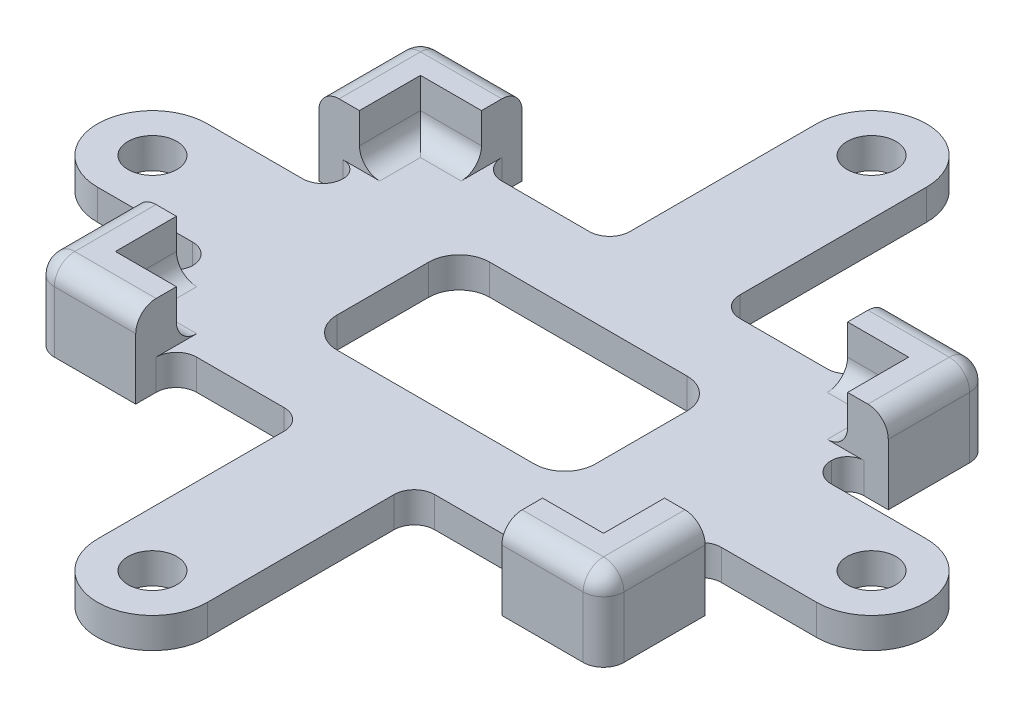
SolidWorks part; units mm, degrees
ref_plane "Front Plane" through (0, 0, 0) normal (0, 0, 1) x (1, 0, 0)
ref_plane "Top Plane" through (0, 0, 0) normal (0, 1, 0) x (1, 0, 0)
ref_plane "Right Plane" through (0, 0, 0) normal (1, 0, 0) x (0, 0, -1)
sketch "Sketch1" plane through (0, 0, 0) normal (0, 1, 0) x (1, 0, 0)
  line L0 (-12, 7.5) -> (12, 7.5)
  line L1 (-11, -6.5) -> (11, -6.5) construction
  line L2 (-11, -6.5) -> (-11, 6.5) construction
  line L3 (-11, 6.5) -> (11, 6.5) construction
  line L4 (11, -6.5) -> (11, 6.5) construction
  line L5 (-11, -6.5) -> (11, 6.5) construction
  line L6 (-11, 6.5) -> (11, -6.5) construction
  line L7 (12, -7.5) -> (12, 7.5)
  line L8 (-12, -7.5) -> (12, -7.5)
  line L9 (-12, -7.5) -> (-12, 7.5)
  point P0 (0, 0)
  point P10 (0, 0)
  point P16 (0, 0)
  dimension "D1" = 13
  dimension "D2" = 22
  dimension "D3" = 1
extrude "Boss-Extrude1" add sketch "Sketch1" along normal mid plane 1.5
sketch "Sketch2" plane through (0, 0.75, 0) normal (0, 1, 0) x (1, 0, 0)
  line L0 (-12, 4.5) -> (-14, 4.5)
  line L1 (-12, 7.5) -> (-12, -7.5) construction
  line L2 (-14, 4.5) -> (-14, 9.5)
  line L3 (-14, 9.5) -> (-9, 9.5)
  line L4 (-9, 9.5) -> (-9, 7.5)
  line L5 (12, 7.5) -> (-12, 7.5) construction
  line L6 (-9, 7.5) -> (-12, 7.5)
  line L7 (-12, 7.5) -> (-12, 4.5)
  dimension "D1" = 3
  dimension "D2" = 2
extrude "Boss-Extrude2" add sketch "Sketch2" along normal blind 2.5 and the other way blind 1.5
mirror "Mirror1" about plane through (0, 0, 0) normal (1, 0, 0) of "Boss-Extrude2"
mirror "Mirror2" about plane through (0, 0, 0) normal (0, 0, 1) of "Mirror1", "Boss-Extrude2"
sketch "Sketch3" plane through (0, 0.75, 0) normal (0, 1, 0) x (1, 0, 0)
  line L0 (0, -17.6777) -> (-17.6777, 0) construction
  line L1 (0, -17.6777) -> (17.6777, 0) construction
  line L2 (-17.6777, 0) -> (0, 17.6777) construction
  line L3 (17.6777, 0) -> (0, 17.6777) construction
  line L4 (0, -17.6777) -> (0, 17.6777) construction
  line L5 (-17.6777, 0) -> (17.6777, 0) construction
  line L6 (-17.6777, 2.7) -> (-12, 2.7)
  line L7 (-12, 4.5) -> (-12, -4.5) construction
  line L8 (-12, 2.7) -> (-12, -2.7)
  line L9 (-12, -2.7) -> (-17.6777, -2.7)
  line L10 (-2.7, 17.6777) -> (-2.7, 7.5)
  line L11 (9, 7.5) -> (-9, 7.5) construction
  line L12 (-2.7, 7.5) -> (2.7, 7.5)
  line L13 (2.7, 7.5) -> (2.7, 17.6777)
  line L14 (12, -2.7) -> (17.6777, -2.7)
  line L15 (12, 2.7) -> (12, -2.7)
  line L16 (17.6777, 2.7) -> (12, 2.7)
  line L17 (-2.7, -7.5) -> (2.7, -7.5)
  line L18 (-2.7, -17.6777) -> (-2.7, -7.5)
  line L19 (2.7, -7.5) -> (2.7, -17.6777)
  circle A0 centre (-17.6777, 0) radius 1.2
  arc A1 (-17.6777, 2.7) -> (-17.6777, -2.7) centre (-17.6777, 0) ccw
  circle A2 centre (-17.6777, 0) radius 2.7 construction
  circle A3 centre (0, 17.6777) radius 1.2
  arc A4 (-2.7, 17.6777) -> (2.7, 17.6777) centre (0, 17.6777) cw
  circle A5 centre (17.6777, 0) radius 1.2
  arc A6 (17.6777, 2.7) -> (17.6777, -2.7) centre (17.6777, 0) cw
  circle A7 centre (0, -17.6777) radius 1.2
  arc A8 (-2.7, -17.6777) -> (2.7, -17.6777) centre (0, -17.6777) ccw
  point P1 (0, 0)
  point P17 (-7.2196, 17.6777)
  dimension "D2" = 2.4
  dimension "D1" = 25
  dimension "D3" = 1.5
extrude "Boss-Extrude3" add sketch "Sketch3" against normal up to surface (1.5 mm away) up to face at (0, -0.75, 0)
fillet "Fillet1" radius 1 28 edges at (-14, 1.25, 9.5) (-14, 3.25, 7) (-11.5, 3.25, 9.5) (14, 1.25, 9.5) (11.5, 3.25, 9.5) (14, 3.25, 7) (14, 1.25, -9.5) (14, 3.25, -7) (11.5, 3.25, -9.5) (-11.5, 3.25, -9.5) (-14, 3.25, -7) (-14, 1.25, -9.5) (-10.5, 0.75, -7.5) (-12, 0.75, -6) (10.5, 0.75, -7.5) (12, 0.75, -6) (12, 0.75, 6) (10.5, 0.75, 7.5) (-10.5, 0.75, 7.5) (-12, 0.75, 6) (2.7, 0, -7.5) (-2.7, 0, -7.5) (-2.7, 0, 7.5) (2.7, 0, 7.5) (12, 0, 2.7) (12, 0, -2.7) (-12, 0, 2.7) (-12, 0, -2.7)
sketch "Sketch4" plane through (0, 0.75, 0) normal (0, 1, 0) x (1, 0, 0)
  line L0 (-13, -4.5) -> (-12, -4.5) construction
  line L1 (-12.8, -4.5) -> (-12, -4.5)
  line L2 (-12, -4.5) -> (-12, -3.7)
  line L3 (-13, 4.5) -> (-12, 4.5) construction
  line L4 (-12.8, 4.5) -> (-12, 4.5)
  line L5 (-12, 4.5) -> (-12, 3.7)
  line L6 (12.8, 4.5) -> (12, 4.5)
  line L7 (12, 4.5) -> (12, 3.7)
  line L8 (13, -4.5) -> (12, -4.5) construction
  line L9 (12, -3.7) -> (12, -4.5)
  line L10 (12, -4.5) -> (12.8, -4.5)
  line L11 (-3.7, 7.5) -> (-9, 7.5) construction
  line L12 (-9, 8.5) -> (-9, 7.5)
  line L13 (-9, 7.5) -> (-8, 7.5)
  line L14 (8, 7.5) -> (9, 7.5)
  line L15 (9, 7.5) -> (9, 8.5)
  line L16 (9, 7.5) -> (9, 8.5) construction
  line L17 (9, 7.5) -> (3.7, 7.5) construction
  line L18 (3.7, -7.5) -> (9, -7.5) construction
  line L19 (9, -7.5) -> (9, -8.5) construction
  line L20 (8, -7.5) -> (9, -7.5)
  line L21 (9, -7.5) -> (9, -8.5)
  line L22 (-9, -7.5) -> (-3.7, -7.5) construction
  line L23 (-9, -8.5) -> (-9, -7.5)
  line L24 (-9, -7.5) -> (-8, -7.5)
  arc A0 (-12, -3.7) -> (-12.8, -4.5) centre (-12.8, -3.7) cw
  arc A1 (-12, -3.7) -> (-13, -2.7) centre (-13, -3.7) ccw construction
  arc A2 (-12, 3.7) -> (-12.8, 4.5) centre (-12.8, 3.7) ccw
  arc A3 (12, 3.7) -> (12.8, 4.5) centre (12.8, 3.7) cw
  arc A4 (12.8, -4.5) -> (12, -3.7) centre (12.8, -3.7) cw
  arc A5 (-8, 7.5) -> (-9, 8.5) centre (-8, 8.5) cw
  arc A6 (9, 8.5) -> (8, 7.5) centre (8, 8.5) cw
  arc A7 (8, -7.5) -> (9, -8.5) centre (8, -8.5) cw
  arc A8 (-9, -8.5) -> (-8, -7.5) centre (-8, -8.5) cw
  dimension "D1" = 0.8
extrude "Boss-Extrude4" add sketch "Sketch4" against normal up to surface (1.5 mm away) up to face at (0, -0.75, 0)
sketch "Sketch5" plane through (0, 0.75, 0) normal (0, 1, 0) x (1, 0, 0)
  line L1 (11, -6.5) -> (-11, -6.5) construction
  line L2 (11, -6.5) -> (11, 6.5) construction
  line L3 (11, 6.5) -> (-11, 6.5) construction
  line L4 (-11, -6.5) -> (-11, 6.5) construction
  line L5 (11, -6.5) -> (-11, 6.5) construction
  line L6 (11, 6.5) -> (-11, -6.5) construction
  line L7 (6.3462, -3.75) -> (-6.3462, -3.75)
  line L8 (6.3462, -3.75) -> (6.3462, 3.75)
  line L9 (6.3462, 3.75) -> (-6.3462, 3.75)
  line L10 (-6.3462, -3.75) -> (-6.3462, 3.75)
  line L11 (6.3462, -3.75) -> (-6.3462, 3.75) construction
  line L12 (6.3462, 3.75) -> (-6.3462, -3.75) construction
  point P0 (0, 0)
  point P6 (0, 0)
  dimension "D1" = 13
  dimension "D2" = 22
  dimension "D3" = 2.75
extrude "Cut-Extrude1" cut sketch "Sketch5" against normal up to surface (1.5 mm away) up to face at (0, -0.75, 0)
fillet "Fillet2" radius 1.5 4 edges at (6.3462, 0, 3.75) (-6.3462, 0, 3.75) (-6.3462, 0, -3.75) (6.3462, 0, -3.75)
